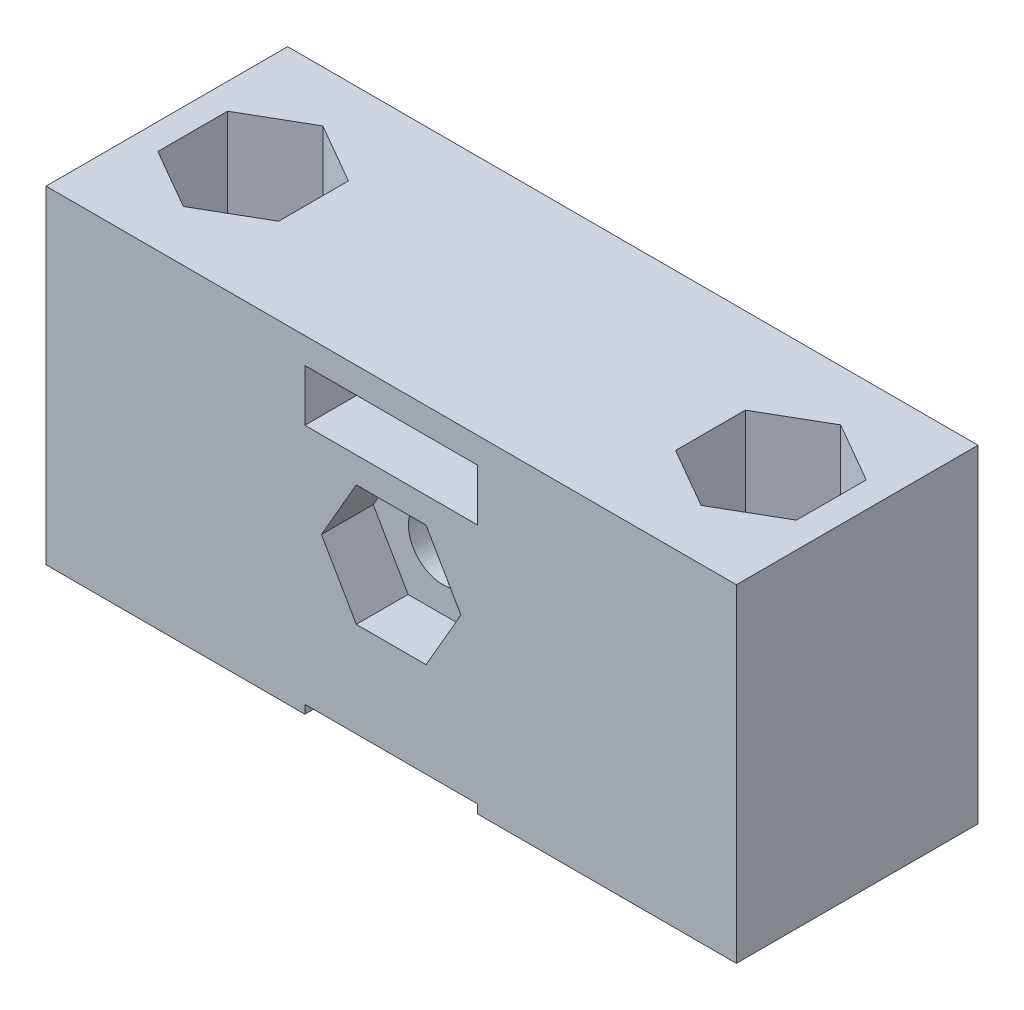
SolidWorks part; units mm, degrees
ref_plane "Front Plane" through (0, 0, 0) normal (0, 0, 1) x (1, 0, 0)
ref_plane "Top Plane" through (0, 0, 0) normal (0, 1, 0) x (1, 0, 0)
ref_plane "Right Plane" through (0, 0, 0) normal (1, 0, 0) x (0, 0, -1)
sketch "Sketch1" plane through (0, 0, 0) normal (0, 1, 0) x (1, 0, 0)
  line L1 (-20, 7) -> (20, 7)
  line L2 (-20, 7) -> (-20, -7)
  line L3 (-20, -7) -> (20, -7)
  line L4 (20, 7) -> (20, -7)
  line L5 (-20, 7) -> (20, -7) construction
  line L6 (-20, -7) -> (20, 7) construction
  point P0 (0, 0)
  dimension "D1" = 40
  dimension "D2" = 14
extrude "Boss-Extrude1" add sketch "Sketch1" along normal blind 19
sketch "Sketch2" plane through (0, 0, 7) normal (0, 0, 1) x (1, 0, 0)
  line L0 (0, 19) -> (0, 0) construction
  line L1 (-20, 19) -> (20, 19) construction
  line L3 (-5, 14.5) -> (5, 14.5)
  line L4 (-5, 14.5) -> (-5, 17.5)
  line L5 (-5, 17.5) -> (5, 17.5)
  line L6 (5, 14.5) -> (5, 17.5)
  line L7 (-5, 14.5) -> (5, 17.5) construction
  line L8 (-5, 17.5) -> (5, 14.5) construction
  line L9 (-5, -0.5) -> (5, -0.5)
  line L10 (-5, -0.5) -> (-5, 0.5)
  line L11 (-5, 0.5) -> (5, 0.5)
  line L12 (5, -0.5) -> (5, 0.5)
  line L13 (-5, -0.5) -> (5, 0.5) construction
  line L14 (-5, 0.5) -> (5, -0.5) construction
  point P5 (0, 16)
  dimension "D1" = 10
  dimension "D2" = 3
  dimension "D3" = 16
  dimension "D4" = 10
  dimension "D5" = 1
extrude "Cut-Extrude1" cut sketch "Sketch2" against normal blind 30
sketch "Sketch3" plane through (0, 0, 7) normal (0, 0, 1) x (1, 0, 0)
  line L0 (0, 19) -> (0, 0) construction
  line L1 (-20, 19) -> (20, 19) construction
  circle A0 centre (0, 9.5) radius 2
  dimension "D1" = 4
extrude "Cut-Extrude2" cut sketch "Sketch3" against normal through all
sketch "Sketch4" plane through (0, 19, 0) normal (0, 1, 0) x (1, 0, 0)
  line L0 (-20, 0) -> (20, 0) construction
  line L1 (-20, 7) -> (-20, -7) construction
  line L2 (20, -7) -> (20, 7) construction
  line L3 (0, 7) -> (0, -7) construction
  line L4 (20, 7) -> (-20, 7) construction
  line L5 (-20, -7) -> (20, -7) construction
  circle A0 centre (-15, 0) radius 1.6
  circle A1 centre (15, 0) radius 1.6
  dimension "D1" = 3.2
  dimension "D2" = 15
extrude "Cut-Extrude3" cut sketch "Sketch4" against normal through all
sketch "Sketch8" plane through (0, 0, 0) normal (0, -1, 0) x (-1, 0, 0)
  line L0 (-5, 7) -> (-5, -7) construction
  line L1 (5, -7) -> (-5, -7)
  line L2 (5, -7) -> (5, -6)
  line L3 (5, -6) -> (-5, -6)
  line L4 (-5, -7) -> (-5, -6)
  dimension "D1" = 1
extrude "Boss-Extrude2" [suppressed] add sketch "Sketch8" against normal up to next
sketch "Sketch9" plane through (0, 19, 0) normal (0, 1, 0) x (1, 0, 0)
  line L0 (0, 7) -> (0, -7) construction
  line L1 (-15, 4.0415) -> (-18.5, 2.0207)
  line L2 (-18.5, 2.0207) -> (-18.5, -2.0207)
  line L3 (-18.5, -2.0207) -> (-15, -4.0415)
  line L4 (-15, -4.0415) -> (-11.5, -2.0207)
  line L5 (-11.5, -2.0207) -> (-11.5, 2.0207)
  line L6 (-11.5, 2.0207) -> (-15, 4.0415)
  line L7 (20, 7) -> (-20, 7) construction
  line L8 (-20, -7) -> (20, -7) construction
  line L9 (11.5, 2.0207) -> (15, 4.0415)
  line L10 (11.5, -2.0207) -> (11.5, 2.0207)
  line L11 (15, -4.0415) -> (11.5, -2.0207)
  line L12 (18.5, -2.0207) -> (15, -4.0415)
  line L13 (18.5, 2.0207) -> (18.5, -2.0207)
  line L14 (15, 4.0415) -> (18.5, 2.0207)
  circle A0 centre (-15, 0) radius 3.5 construction
  circle A1 centre (15, 0) radius 3.5 construction
  dimension "D1" = 7
extrude "Cut-Extrude4" cut sketch "Sketch9" against normal blind 10
sketch "Sketch10" plane through (0, 0, 7) normal (0, 0, 1) x (1, 0, 0)
  line L1 (2.0207, 13) -> (-2.0207, 13)
  line L2 (-2.0207, 13) -> (-4.0415, 9.5)
  line L3 (-4.0415, 9.5) -> (-2.0207, 6)
  line L4 (-2.0207, 6) -> (2.0207, 6)
  line L5 (2.0207, 6) -> (4.0415, 9.5)
  line L6 (4.0415, 9.5) -> (2.0207, 13)
  circle A0 centre (0, 9.5) radius 3.5 construction
  dimension "D1" = 7
extrude "Cut-Extrude5" cut sketch "Sketch10" against normal blind 3
equation "\"X-ROD-SPACING\"=45"
equation "\"Y-ROD-SPACING\"=75"
equation "\"Z-ROD-SPACING\"=17.5"
equation "\"Y-BED-OFFSET\"=2"
equation "\"Y-BED-ROD-INSET\"=3.5"
equation "\"Y-BED-SCREW-SPACING\"=209"
equation "\"Y-BED-SCREW-CUTOUT-SLOT-HEIGHT\"=2"
equation "\"T-SLOT-NUT-FILLET-RADIUS\"=0.25"
equation "\"T-SLOT-SCREW-SHAFT-RADIUS\"=1.75"
equation "\"T-SLOT-SCREW-SHAFT-CUTOUT-LENGTH\"=10.5"
equation "\"T-SLOT-NUT-DEPTH\"=4.2"
equation "\"T-SLOT-NUT-WIDTH\"=3"
equation "\"T-SLOT-NUT-END-DISTANCE\"=8"
equation "\"ACRYLIC-THICKNESS\"=10"
equation "\"ACRYLIC-THICKNESS2\"=4.5"
equation "\"ACRYLIC-TAB-CUTOUT-SIZE\"=\"ACRYLIC-THICKNESS\"+\"ACRYLIC-TAB-TOLERANCE\"*2"
equation "\"ACRYLIC-TAB-TOLERANCE\"=.1"
equation "\"ACRYLIC-TAB-WIDTH\"=\"ACRYLIC-THICKNESS\""
equation "\"ACRYLIC-M3-HOLE\"=3.1"
equation "\"SMOOTHROD-CAP-SCREW-DISTANCE\"=20"
equation "\"FRAME-WIDTH-INNER\"=370"
equation "\"NEMA17-HOLE-SPACING\"=31"
equation "\"NEMA17-CENTRAL-CUTOUT\"=22.5"
equation "\"Z-BRACKET-REACH\"=55"
equation "\"Z-ROD-INSET\"=16"
equation "\"TOP-BRACKET-SPACING\"=40"
equation "\"SMOOTHROD-X-LENGTH\"=350"
equation "\"SMOOTHROD-Y-LENGTH\"=350"
equation "\"SMOOTHROD-Z-LENGTH\"=350"
equation "\"SMOOTHROD-TIGHTENING-HEADROOM\"=.25"
equation "\"LEADSCREW-Z-LENGTH\"=300"
equation "\"SCREW-LENGTH-FRAME\"=\"ACRYLIC-THICKNESS\" + 10"
equation "\"SCREW-LENGTH-MOTOR\"=\"ACRYLIC-THICKNESS\" + 5"
equation "\"SCREW-LENGTH-EXTRUDER\"=28"
equation "\"SCREW-HEAD-RADIUS\"=6"
equation "\"PRINTED-M3-HOLE\"=3.5"
equation "\"PRINTED-X-SMOOTHROD-DIAMETER\"=8.2"
equation "\"PRINTED-X-SMOOTHROD-CUTOUT\"=10"
equation "\"PRINTED-X-BASE-HEIGHT\"=10"
equation "\"PRINTED-LM8UU-CUTOUT-SIZE\"=15.25"
equation "\"PRINTED-LM8UU-CUTOUT-LENGTH\"=24.5"
equation "\"PRINTED-X-IDLER-HEIGHT\"=16"
equation "\"PSU-MOUNTING-WIDTH\"=95"
equation "\"PSU-MOUNTING-HEIGHT\"=177"
equation "\"Y-BELT-TO-ROD-DISTANCE\"=20"
equation "\"SPOOL-HOLDER-ROD-SPACING\"=150"
equation "\"ACRYLIC-X-CARRIAGE-WIDTH\"=55"
equation "\"ACRYLIC-X-CARRIAGE-HEIGHT\"=75"
equation "\"ACRYLIC-X-CARRIAGE-LM8UU-CUTOUT-WIDTH\"=24.25"
equation "\"ACRYLIC-X-CARRIAGE-LM8UU-CUTOUT-HEIGHT\"=11.5"
equation "\"ACRYLIC-X-CARRIAGE-SCREW-SPACING-X\"=15"
equation "\"ACRYLIC-X-CARRIAGE-SCREW-SPACING-Y\"=33"
equation "\"ACRYLIC-X-CARRIAGE-CENTER-TAB-SPACING\"=14"
equation "\"ACRYLIC-X-CARRIAGE-EXTRUDER-OFFSET\"=26"
equation "\"ACRYLIC-X-CARRIAGE-EXTRUDER-ANGLE\"=90"
equation "\"ACRYLIC-X-CARRIAGE-EXTRUDER-SHELF-DEPTH\"=\"ACRYLIC-X-CARRIAGE-EXTRUDER-OFFSET\" + 28"
equation "\"ACRYLIC-X-CARRIAGE-EXTRUDER-BRACE-SPACING\"=23"
equation "\"ACRYLIC-X-CARRIAGE-EXTRUDER-BRACE-TAB-OFFSET\"=20"
equation "\"ACRYLIC-X-CARRIAGE-EXTRUDER-BRACE-HEIGHT\"=35"
equation "\"ACRYLIC-X-CARRIAGE-EXTRUDER-BRACE-SCREW-SPACING\"=22"
equation "\"ACRYLIC-X-CARRIAGE-DUAL-WIDTH-MULTIPLIER\"=1.65"
equation "\"ACRYLIC-X-CARRIAGE-DUAL-HOTEND-SPACING\"=42"
equation "\"ACRYLIC-X-CARRIAGE-DUAL-WIDTH\"=103"
equation "\"ACRYLIC-X-CARRIAGE-DUAL-HOTEND-SEPARATION\"=35"
equation "\"ACRYLIC-X-CARRIAGE-DUAL-MOUNT-PLATE-DEPTH\"=76"
equation "\"ACRYLIC-X-CARRIAGE-DUAL-MOUNT-BRACE-WIDTH\"=45"
equation "\"ACRYLIC-X-CARRIAGE-DUAL-MOUNT-SCREW-WIDTH\"=40"
equation "\"BLOWER-FAN-WIDTH\"=15"
equation "\"PRINTED-M3-NUT-AF\"=7"
equation "\"D1@Sketch9\"=\"PRINTED-M3-NUT-AF\""
equation "\"D1@Sketch10\"=\"PRINTED-M3-NUT-AF\""
